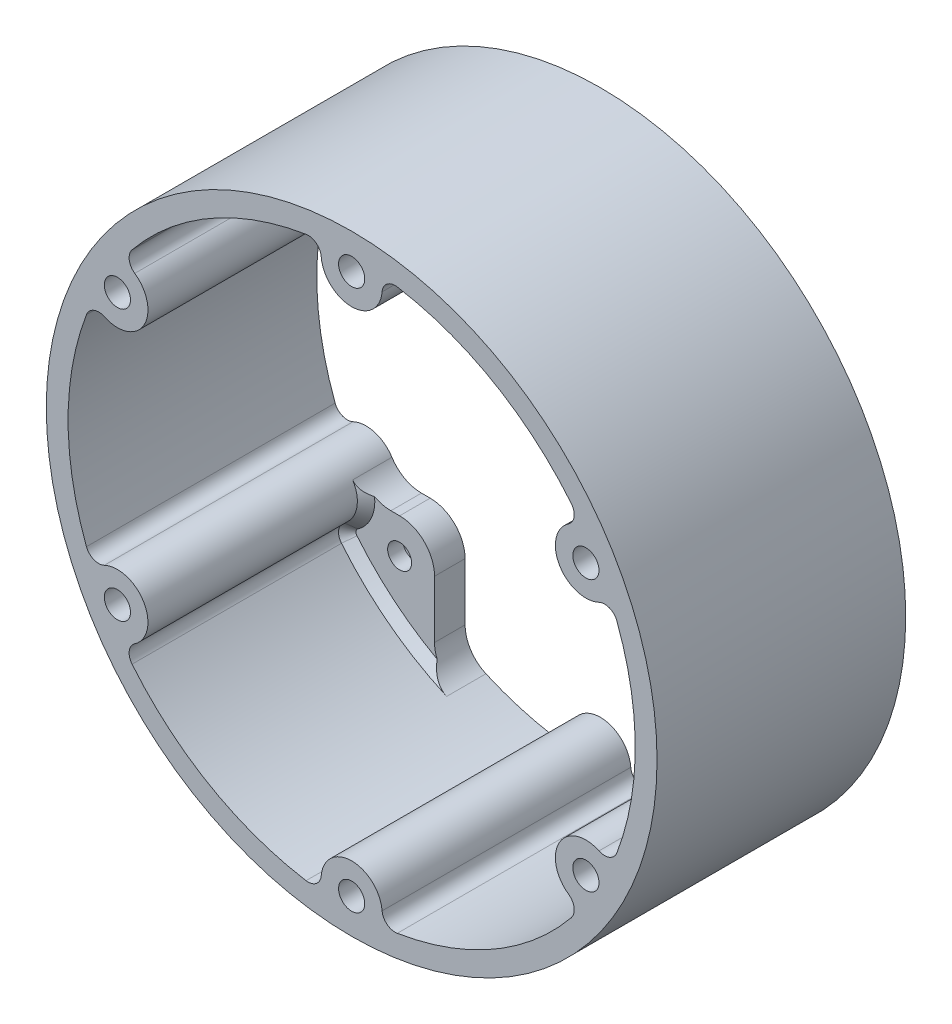
SolidWorks part; units mm, degrees
ref_plane "Спереди" through (0, 0, 0) normal (0, 0, 1) x (1, 0, 0)
ref_plane "Сверху" through (0, 0, 0) normal (0, 1, 0) x (1, 0, 0)
ref_plane "Справа" through (0, 0, 0) normal (1, 0, 0) x (0, 0, -1)
sketch "Эскиз1" plane through (0, 0, 0) normal (0, 0, 1) x (1, 0, 0)
  circle A1 centre (0, 0) radius 70
  circle A2 centre (0, 0) radius 65
  dimension "D2" = 140
  dimension "D1" = 5
extrude "Бобышка-Вытянуть1" add sketch "Эскиз1" along normal blind 57
sketch "Эскиз2" plane through (0, 0, 0) normal (0, 0, -1) x (-1, 0, 0)
  circle A0 centre (0, 62) radius 7
  circle A1 centre (0, 62) radius 3
  dimension "D1" = 14
  dimension "D2" = 6
  dimension "D3" = 62
extrude "Бобышка-Вытянуть2" add sketch "Эскиз2" against normal up to surface (57 mm away) up to face at (70, 0, 57)
pattern_circular "Круговой массив1" count 6 over 360 about axis through (0, 0, 57) along (0, 0, -1) of "Бобышка-Вытянуть2"
fillet "Скругление1" radius 3 12 edges at (52.7784, -37.9399, 28.5) (59.2461, -26.7375, 28.5) (52.7784, 37.9399, 28.5) (59.2461, 26.7375, 28.5) (6.4677, 64.6774, 28.5) (-6.4677, 64.6774, 28.5) (-52.7784, 37.9399, 28.5) (-59.2461, 26.7375, 28.5) (-59.2461, -26.7375, 28.5) (-52.7784, -37.9399, 28.5) (-6.4677, -64.6774, 28.5) (6.4677, -64.6774, 28.5)
sketch "Эскиз3" plane through (0, 0, 0) normal (0, 0, -1) x (-1, 0, 0)
  line L1 (31, -31) -> (46.6936, -31)
  line L2 (31, -31) -> (31, -57.1314)
  arc A0 (10.4497, -64.1545) -> (50.3346, -41.127) centre (0, 0) ccw construction
  arc A1 (56.6933, -24.6753) -> (49.7161, -36.7602) centre (53.6936, -31) ccw construction
  arc A2 (50.3346, -41.127) -> (49.7161, -36.7602) centre (48.0115, -39.2288) ccw construction
  arc A3 (46.6936, -31) -> (49.7161, -36.7602) centre (53.6936, -31) ccw
  arc A4 (50.3346, -41.127) -> (49.7161, -36.7602) centre (48.0115, -39.2288) ccw
  arc A5 (31, -57.1314) -> (50.3346, -41.127) centre (0, 0) ccw
  dimension "D1" = 31
  dimension "D2" = 31
extrude "Бобышка-Вытянуть3" add sketch "Эскиз3" against normal blind 7
mirror "Зеркальное отражение1" about plane through (0, 0, 0) normal (0, 1, 0) of "Бобышка-Вытянуть3"
mirror "Зеркальное отражение2" about plane through (0, 0, 0) normal (1, 0, 0) of "Зеркальное отражение1", "Бобышка-Вытянуть3"
hole_wizard "Цековка для винта с внутренним шестигранником M51" positions "Эскиз5" profile "Эскиз4" counterbore size "M5" standard "Ansi Metric" end condition through all
sketch "Эскиз5" plane through (0, 0, 0) normal (0, 0, -1) x (-1, 0, 0)
  line L1 (39, -39) -> (-39, -39) construction
  line L2 (39, -39) -> (39, 39) construction
  line L3 (39, 39) -> (-39, 39) construction
  line L4 (-39, -39) -> (-39, 39) construction
  line L5 (39, -39) -> (-39, 39) construction
  line L6 (39, 39) -> (-39, -39) construction
  point P0 (39, 39)
  point P2 (-39, 39)
  point P4 (-39, -39)
  point P6 (39, -39)
  point P9 (0, 0)
  dimension "D1" = 78
  dimension "D2" = 78
sketch "Эскиз4" plane through (-39, 39, 0) normal (1, 0, 0) x (0, 1, 0)
  line L0 (0, 0) -> (0, 57)
  line L1 (0, 57) -> (2.75, 57)
  line L3 (2.75, 57) -> (2.75, 3.5)
  line L4 (2.75, 3.5) -> (5, 3.5)
  line L5 (5, 3.5) -> (5, 0)
  line L7 (5, 0) -> (0, 0)
  line L11 (0, -6.35) -> (0, 107.95) construction
  dimension "Диаметр сквозного отверстия" = 5.5
  dimension "Глубина сквозного отверстия" = 57
  dimension "Диаметр цековки" = 10
  dimension "Глубина цековки" = 3.5
fillet "Скругление2" radius 8 12 edges at (31, -31, 3.5) (-31, -31, 3.5) (-31, 31, 3.5) (31, 31, 3.5) (46.6936, -31, 3.5) (31, -57.1314, 3.5) (-31, -57.1314, 3.5) (-46.6936, -31, 3.5) (-46.6936, 31, 3.5) (-31, 57.1314, 3.5) (46.6936, 31, 3.5) (31, 57.1314, 3.5)
chamfer "Фаска2" distance 2 angle 45 12 edges at (39.3651, -51.7242, 7) (50.9818, -38.8081, 7) (46.8359, -32.4042, 7) (-46.8359, -32.4042, 7) (-50.9818, -38.8081, 7) (-39.3651, -51.7242, 7) (-46.8359, 32.4042, 7) (-50.9818, 38.8081, 7) (-39.3651, 51.7242, 7) (46.8359, 32.4042, 7) (50.9818, 38.8081, 7) (39.3651, 51.7242, 7)
sketch "Эскиз6" plane through (0, 0, 3.5) normal (0, 0, -1) x (-1, 0, 0)
  circle A0 centre (39, 39) radius 2.75 construction
  circle A1 centre (39, 39) radius 2.75
  circle A2 centre (-39, 39) radius 2.75 construction
  circle A3 centre (-39, 39) radius 2.75
  circle A4 centre (-39, -39) radius 2.75 construction
  circle A5 centre (-39, -39) radius 2.75
  circle A6 centre (39, -39) radius 2.75 construction
  circle A7 centre (39, -39) radius 2.75
extrude "Бобышка-Вытянуть4" [suppressed] add sketch "Эскиз6" against normal blind 0.15
